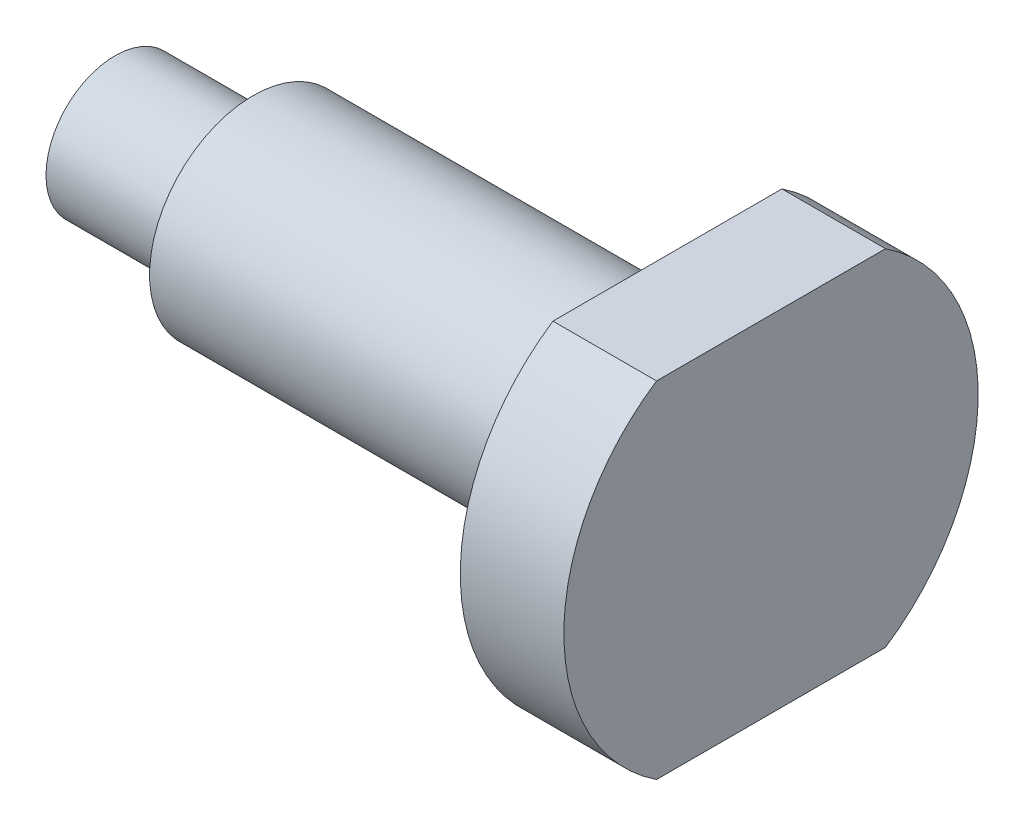
SolidWorks part; units mm, degrees
material "201 Annealed Stainless Steel (SS)"
ref_plane "Front Plane" through (0, 0, 0) normal (0, 0, 1) x (1, 0, 0)
ref_plane "Top Plane" through (0, 0, 0) normal (0, 1, 0) x (1, 0, 0)
ref_plane "Right Plane" through (0, 0, 0) normal (1, 0, 0) x (0, 0, -1)
sketch "Sketch2" plane through (0, 0, 0) normal (1, 0, 0) x (0, 0, -1)
  line L1 (3.3166, 5) -> (-3.3166, 5)
  line L2 (3.3166, -5) -> (-3.3166, -5)
  arc A0 (-3.3166, 5) -> (-3.3166, -5) centre (0, 0) ccw
  circle A1 centre (0, 0) radius 3
  circle A2 centre (0, 0) radius 2
  arc A3 (3.3166, -5) -> (3.3166, 5) centre (0, 0) ccw
  point P9 (-3.2245, 3.8213)
  dimension "D1" = 12
  dimension "D2" = 6
  dimension "D3" = 4
  dimension "D4" = 5
  dimension "8" = 10
extrude "Boss-Extrude1" add sketch "Sketch2" along normal blind 3 contours L2 A3 L1 A0 A1 | A1 A2 | A2 region at (0, 0, -5.8438) region at (0, 0, 2.9151) region at (0, 0, 0)
extrude "Boss-Extrude2" add sketch "Sketch2<3>" against normal blind 12 contours A1 A2 | A2 region at (0, 0, 2.9151) region at (0, 0, 0)
sketch "Sketch2<3>" plane through (0, 0, 0) normal (1, 0, 0) x (0, 0, -1) same geometry as "Sketch2"
sketch "Sketch3" plane through (-12, 0, 0) normal (-1, 0, 0) x (0, 0, 1)
  circle A0 centre (0, 0) radius 2 construction
  circle A1 centre (0, 0) radius 2
extrude "Boss-Extrude3" add sketch "Sketch3" along normal blind 4
cosmetic thread "Cosmetic Thread1" parameters "D2"=3.22
